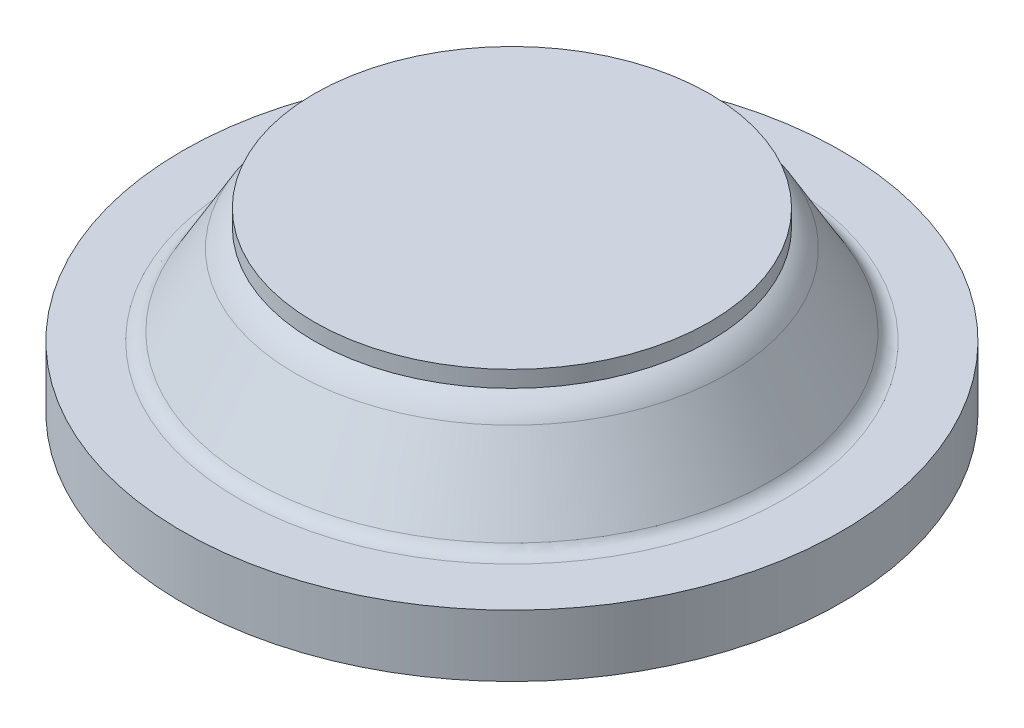
SolidWorks part; units mm, degrees
ref_plane "Front Plane" through (0, 0, 0) normal (0, 0, 1) x (1, 0, 0)
ref_plane "Top Plane" through (0, 0, 0) normal (0, 1, 0) x (1, 0, 0)
ref_plane "Right Plane" through (0, 0, 0) normal (1, 0, 0) x (0, 0, -1)
sketch "Sketch1" plane through (0, 0, 0) normal (0, 0, 1) x (1, 0, 0)
  line L0 (0, 0) -> (0, -15.24)
  line L1 (0, -15.24) -> (40.64, -15.24)
  line L2 (40.64, -15.24) -> (31.75, 0)
  line L3 (31.75, 0) -> (0, 0)
  dimension "D1" = 31.75
  dimension "D2" = 40.64
  dimension "D3" = 15.24
  dimension "D4" = 0
revolve "Revolve1" add sketch "Sketch1" angle 360 about L0
sketch "Sketch3" plane through (0, 0, 0) normal (0, 1, 0) x (1, 0, 0)
  circle A0 centre (0, 0) radius 30.48
  dimension "D1" = 60.96
extrude "Boss-Extrude1" add sketch "Sketch3" along normal blind 2.54 contours A0
sketch "Sketch6" plane through (0, -15.24, 0) normal (0, -1, 0) x (1, 0, 0)
  circle A0 centre (0, 0) radius 50.8
  dimension "D1" = 101.6
extrude "Boss-Extrude2" add sketch "Sketch6" along normal blind 9.525
fillet "Fillet2" radius 2.54 1 edges at (40.64, -15.24, 0)
fillet "Fillet1" radius 7.62 1 edges at (-31.75, 0, 0)
